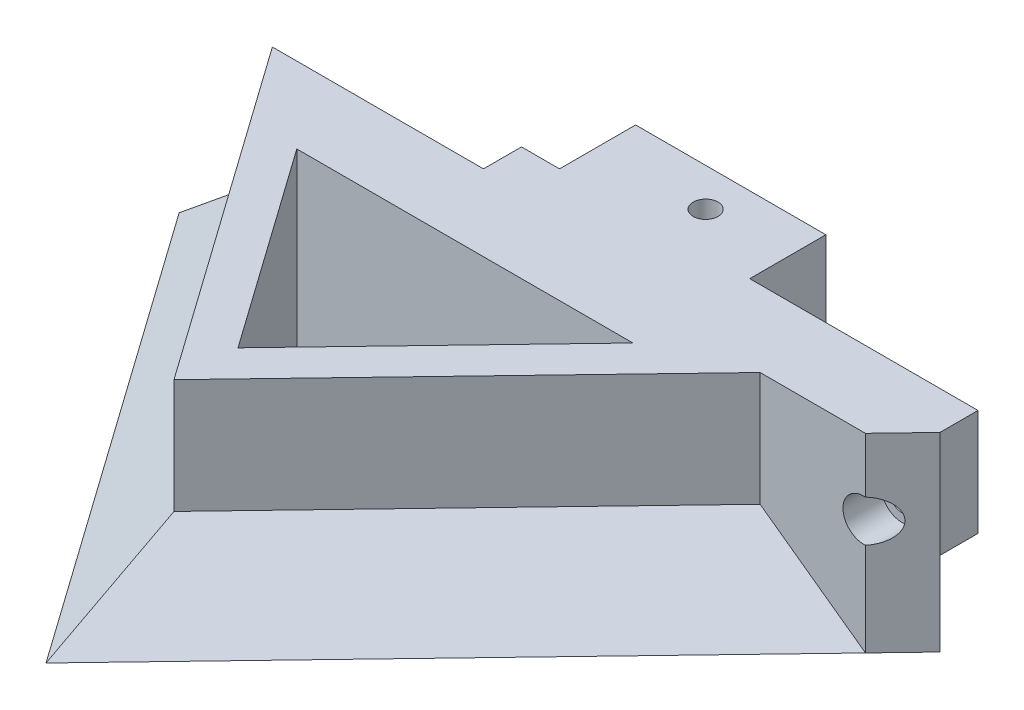
SolidWorks part; units mm, degrees
ref_plane "Front Plane" through (0, 0, 0) normal (0, 0, 1) x (1, 0, 0)
ref_plane "Top Plane" through (0, 0, 0) normal (0, 1, 0) x (1, 0, 0)
ref_plane "Right Plane" through (0, 0, 0) normal (1, 0, 0) x (0, 0, -1)
sketch "Sketch2" plane through (0, 0, 0) normal (0, 1, 0) x (1, 0, 0)
  line L0 (0, 0) -> (0, -76.2) construction
  line L1 (-69.85, 0) -> (0, 0) construction
  line L2 (-69.85, 6.35) -> (-76.2, 6.35)
  line L3 (-76.2, 6.35) -> (-76.2, 0)
  line L4 (-76.2, 0) -> (-69.85, 0) construction
  line L5 (-76.2, 0) -> (-127, 0)
  line L6 (-73.025, 0) -> (-73.025, -76.2) construction
  line L7 (-127, 0) -> (-73.025, -76.2)
  line L8 (-73.025, -76.2) -> (0, 0)
  line L9 (-38.5563, -12.7) -> (-69.85, -12.7)
  line L10 (-76.2, -12.7) -> (-69.85, -12.7)
  line L11 (-76.2, -12.7) -> (-94.6593, -12.7)
  line L12 (-69.85, 0) -> (-69.85, 6.35) construction
  line L13 (-69.85, 6.35) -> (-69.85, 19.05)
  line L14 (-69.85, 19.05) -> (-38.1, 19.05)
  line L15 (-38.1, 19.05) -> (-38.1, 6.35)
  line L16 (-38.1, 6.35) -> (-38.1, 0) construction
  line L17 (-69.85, 6.35) -> (-38.1, 6.35) construction
  line L18 (-69.85, 12.7) -> (-51.816, 12.7) construction
  line L20 (-70.8155, -46.3618) -> (-38.5563, -12.7)
  line L21 (0, 0) -> (0, 6.35)
  line L22 (-38.1, 6.35) -> (0, 6.35)
  line L23 (0, 6.35) -> (6.0854, 6.35) construction
  line L24 (-94.6593, -12.7) -> (-70.8155, -46.3618)
  line L25 (0, 0) -> (6.0854, 6.35) construction
  line L26 (-111.4547, 11.0112) -> (-70.8155, -46.3618) construction
  line L27 (-70.8155, -46.3618) -> (-13.7539, 13.1808) construction
  circle A0 centre (-51.816, 12.7) radius 2.0828
  point P21 (-99.1973, -12.7)
  point P27 (-27.8144, -12.7)
  point P28 (-38.1, -12.7)
  point P29 (-94.8151, -12.7)
  point P30 (-94.6593, -12.7)
  point P31 (-38.5563, -12.7)
  dimension "D2" = 69.85
  dimension "D3" = 6.35
  dimension "D4" = 50.8
extrude "Boss-Extrude1" add sketch "Sketch2" along normal blind 31.75
sketch "Sketch3" plane through (0, 31.75, 0) normal (0, 1, 0) x (1, 0, 0)
  line L0 (-127, 0) -> (-73.025, -76.2)
  line L1 (-73.025, -76.2) -> (-6.0854, -6.35)
  line L2 (-23.6757, -6.35) -> (-6.0854, -6.35)
  line L3 (-38.5563, -12.7) -> (-26.3855, 0) construction
  line L5 (-111.4367, 0) -> (-127, 0)
  line L6 (-94.6593, -12.7) -> (-103.6551, 0) construction
  line L7 (-71.552, -56.3079) -> (-111.4367, 0)
  line L8 (-76.2, 0) -> (-127, 0) construction
  line L11 (-71.552, -56.3079) -> (-23.6757, -6.35)
sketch "Sketch4" plane through (0, 0, 0) normal (0, -1, 0) x (1, 0, 0)
  line L0 (-38.1, -6.35) -> (-69.85, -6.35)
  line L1 (-69.85, -6.35) -> (-69.85, -19.05)
  line L2 (-69.85, -19.05) -> (-38.1, -19.05)
  line L3 (-38.1, -19.05) -> (-38.1, -6.35)
extrude "Cut-Extrude1" cut sketch "Sketch4" against normal blind 19.05
sketch "Sketch5" plane through (0, 19.05, 0) normal (0, -1, 0) x (-1, 0, 0)
  circle A0 centre (51.816, 12.7) radius 2.0828 construction
  circle A1 centre (51.816, 12.7) radius 3.4925
extrude "Cut-Extrude2" cut sketch "Sketch5" against normal blind 6.35
sketch "Sketch6" plane through (0, 0, -6.35) normal (0, 0, -1) x (-1, 0, 0)
  line L1 (0, 31.75) -> (0, 0) construction
  line L3 (6.35, 31.75) -> (6.35, 19.05) construction
  line L4 (0, 31.75) -> (38.1, 31.75) construction
  line L5 (0, 19.05) -> (6.35, 19.05) construction
  circle A0 centre (6.35, 19.05) radius 3.4925
extrude "Cut-Extrude6" cut sketch "Sketch3" against normal blind 19.05
chamfer "Chamfer5" distance 12.7 angle 45 1 edges at (-39.5552, 12.7, 41.275)
chamfer "Chamfer7" distance 12.7 angle 45 1 edges at (-103.7504, 12.7, 32.8229)
extrude "Cut-Extrude8" cut sketch "Sketch6" against normal blind 25.4
sketch "Sketch15" plane through (0, 0, -6.35) normal (0, 0, -1) x (-1, 0, 0)
  circle A0 centre (6.35, 19.05) radius 3.4925
  circle A1 centre (6.35, 19.05) radius 2.0828
extrude "Boss-Extrude2" add sketch "Sketch15" against normal blind 6.35
sketch "Sketch14" plane through (0, 0, -6.35) normal (0, 0, -1) x (-1, 0, 0)
  line L0 (0, 0) -> (11.43, 0)
  line L1 (0, 0) -> (76.2, 0) construction
  line L2 (11.43, 0) -> (11.43, 13.97)
  line L3 (11.43, 13.97) -> (0, 13.97)
  line L4 (0, 31.75) -> (0, 0) construction
  line L5 (0, 13.97) -> (0, 0)
extrude "Cut-Extrude10" cut sketch "Sketch14" against normal blind 6.35
